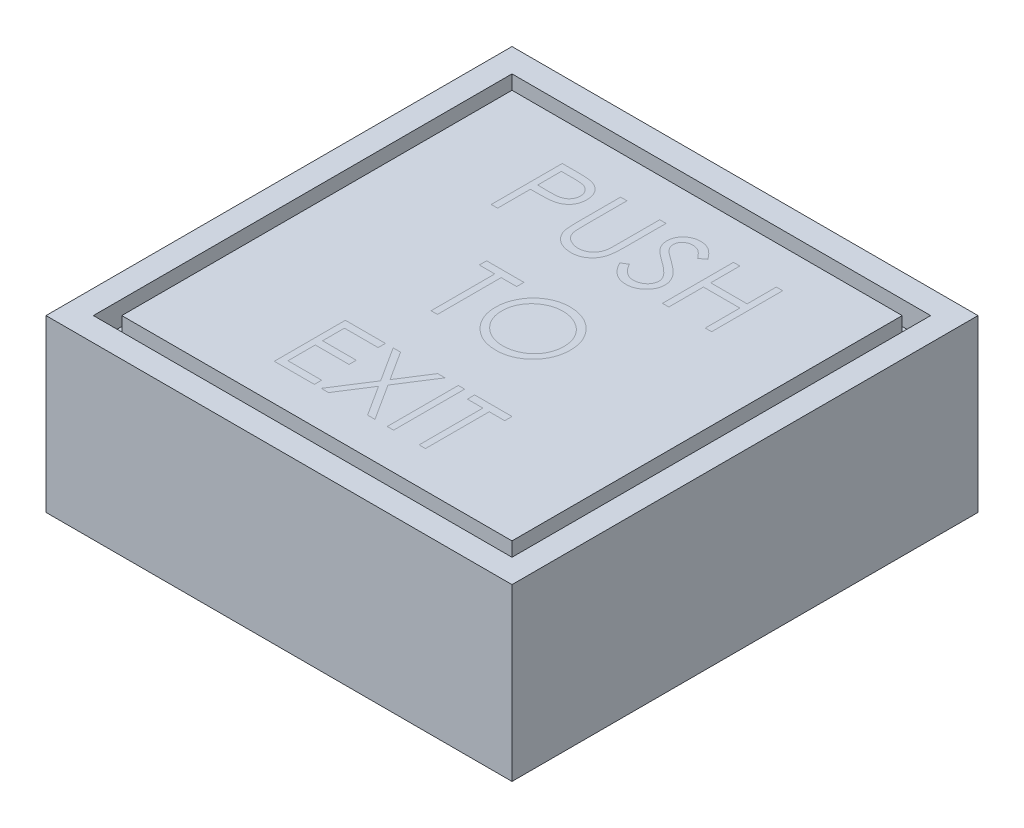
SolidWorks part; units mm, degrees
material "Stainless Steel (ferritic)"
ref_plane "Front Plane" through (0, 0, 0) normal (0, 0, 1) x (1, 0, 0)
ref_plane "Back of Button Plane" through (0, 0, 0) normal (0, 1, 0) x (1, 0, 0)
ref_plane "Right Plane" through (0, 0, 0) normal (1, 0, 0) x (0, 0, -1)
sketch "Sketch1" plane through (0, 0, 0) normal (0, 1, 0) x (1, 0, 0)
  line L1 (0, 0) -> (124.968, 0)
  line L2 (0, 0) -> (0, 124.968)
  line L3 (0, 124.968) -> (124.968, 124.968)
  line L4 (124.968, 0) -> (124.968, 124.968)
  dimension "D1" = 124.968
  dimension "D2" = 124.968
extrude "Boss-Extrude1" add sketch "Sketch1" along normal blind 45.72
sketch "Sketch4" plane through (0, 45.72, 0) normal (0, 1, 0) x (1, 0, 0)
  line L8 (6.35, 118.618) -> (6.35, 6.35)
  line L9 (6.35, 6.35) -> (118.618, 6.35)
  line L10 (118.618, 6.35) -> (118.618, 118.618)
  line L11 (118.618, 118.618) -> (6.35, 118.618)
  line L12 (6.35, 118.618) -> (6.35, 6.35)
  line L13 (6.35, 6.35) -> (118.618, 6.35)
  line L14 (118.618, 6.35) -> (118.618, 118.618)
  line L15 (118.618, 118.618) -> (6.35, 118.618)
  dimension "D1" = 6.35
extrude "Cut-Extrude1" cut sketch "Sketch4" against normal blind 6.35
sketch "Sketch6" plane through (0, 39.37, 0) normal (0, 1, 0) x (1, 0, 0)
  line L8 (114.808, 10.16) -> (114.808, 114.808)
  line L9 (10.16, 10.16) -> (114.808, 10.16)
  line L10 (10.16, 114.808) -> (10.16, 10.16)
  line L11 (114.808, 114.808) -> (10.16, 114.808)
  line L12 (114.808, 10.16) -> (114.808, 114.808)
  line L13 (10.16, 10.16) -> (114.808, 10.16)
  line L14 (10.16, 114.808) -> (10.16, 10.16)
  line L15 (114.808, 114.808) -> (10.16, 114.808)
  dimension "D1" = 3.81
extrude "Boss-Extrude2" add sketch "Sketch6" along normal blind 6.35
sketch "Sketch11" plane through (0, 45.72, 0) normal (0, 1, 0) x (1, 0, 0)
  text T0 "PUSH \r\n  TO\r\n EXIT" font "Century Gothic" height in points 72
  point P1 (0, 0)
  point P2 (0, 0)
wrap "Wrap1" sketch "Sketch11" wrap type scribe source sketch "Sketch11" face at (62.484, 45.72, -62.484)
